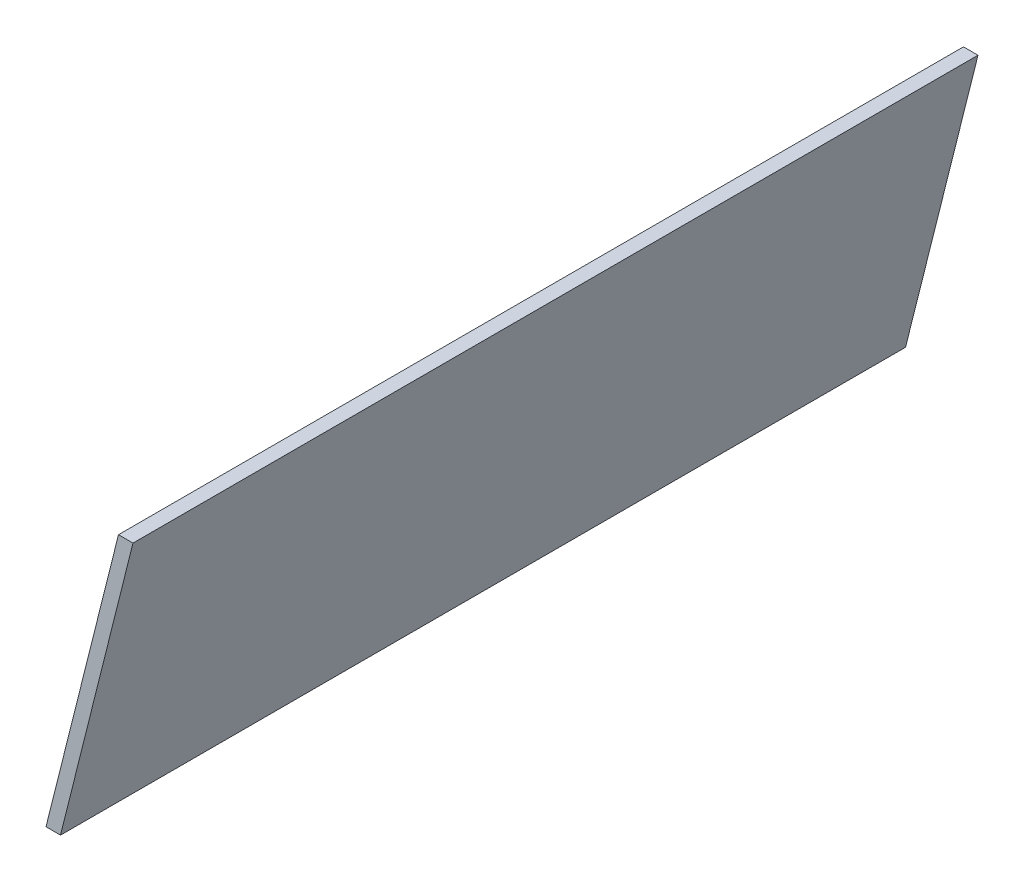
SolidWorks part; units mm, degrees
material "5052-H32"
ref_plane "Front Plane" through (0, 0, 0) normal (0, 0, 1) x (1, 0, 0)
ref_plane "Top Plane" through (0, 0, 0) normal (0, 1, 0) x (1, 0, 0)
ref_plane "Right Plane" through (0, 0, 0) normal (1, 0, 0) x (0, 0, -1)
sketch "Sketch1" plane through (0, 0, 0) normal (0, 0, 1) x (1, 0, 0)
  line L0 (-40.9017, -38.8249) -> (-36.1392, -38.8249)
  line L1 (-36.1392, -38.8249) -> (-12.339, 56.1381)
  line L2 (-40.9017, -38.8249) -> (-17.1015, 56.1381)
  line L3 (-12.339, 56.1381) -> (-17.1015, 56.1381)
  dimension "D1" = 104.07
extrude "Boss-Extrude1" add sketch "Sketch1" along normal blind 277.475 contours L1 L3 L2 L0
